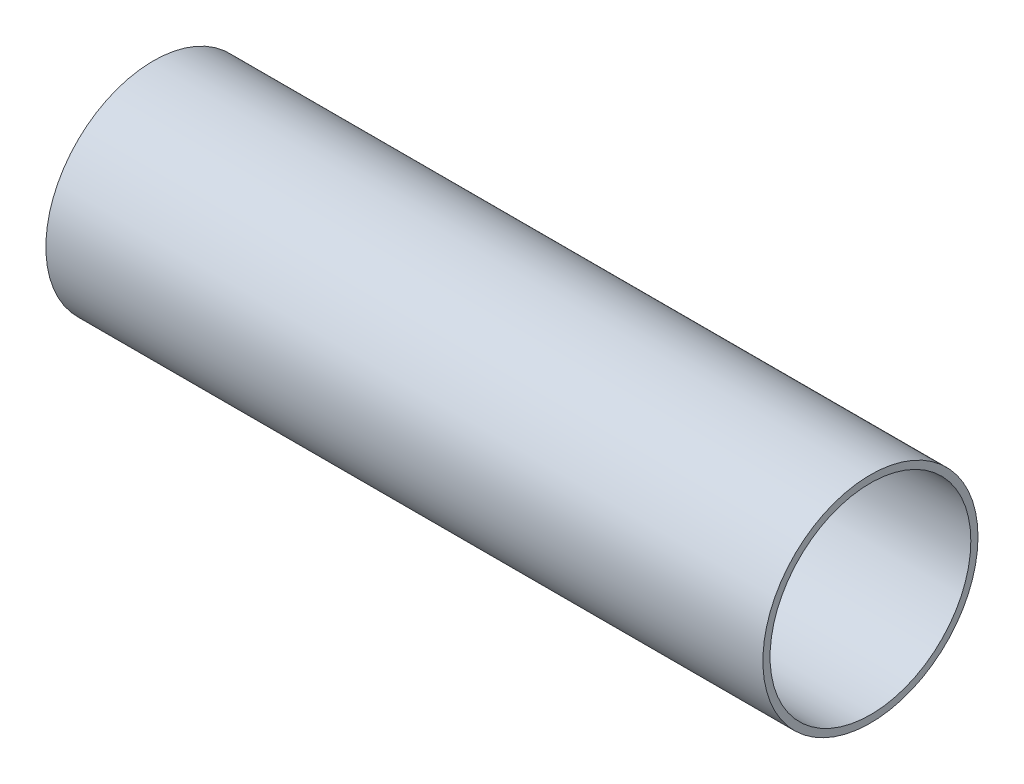
SolidWorks part; units mm, degrees
material "炭素鋼(普通)"
ref_plane "HOR" through (0, 0, 0) normal (0, 0, 1) x (1, 0, 0)
ref_plane "VERT" through (0, 0, 0) normal (0, 1, 0) x (1, 0, 0)
ref_plane "CTR" through (0, 0, 0) normal (1, 0, 0) x (0, 0, -1)
ref_axis "A_X" through (210, 0, 0) along (-1, 0, 0)
ref_axis "A_Y" through (0, 33, 0) along (0, -1, 0)
ref_axis "A_Z" through (0, 0, 33) along (0, 0, -1)
sketch3d "PNT_CG"
  point P0 (0, 0, 0)
sketch "Sketch1" plane through (0, 0, 0) normal (1, 0, 0) x (0, 0, -1)
  circle A0 centre (0, 0) radius 30
  dimension "D1" = 60
extrude "Boss-Extrude1" add sketch "Sketch1" along normal blind 200
sketch "Sketch3" plane through (200, 0, 0) normal (1, 0, 0) x (0, 0, -1)
  circle A0 centre (0, 0) radius 28
  dimension "D1" = 56
extrude "Cut-Extrude1" cut sketch "Sketch3" against normal blind 200
